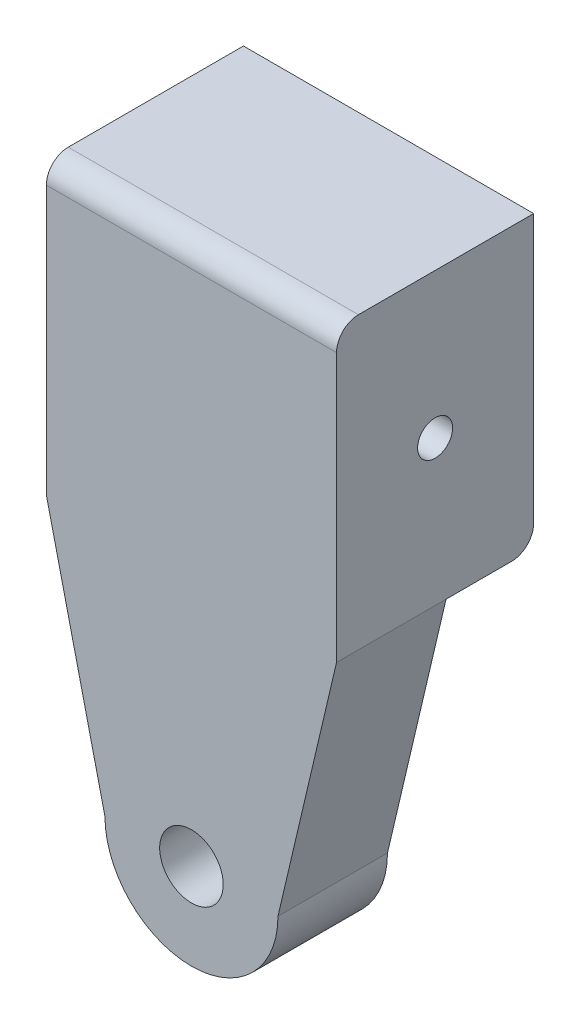
SolidWorks part; units mm, degrees
ref_plane "Alzado" through (0, 0, 0) normal (0, 0, 1) x (1, 0, 0)
ref_plane "Planta" through (0, 0, 0) normal (0, 1, 0) x (1, 0, 0)
ref_plane "Vista lateral" through (0, 0, 0) normal (1, 0, 0) x (0, 0, -1)
sketch "Croquis1" plane through (0, 0, 0) normal (0, 0, 1) x (1, 0, 0)
  line L0 (13.25, 13.25) -> (-13.25, 13.25)
  line L1 (10.25, -10.25) -> (-10.25, -10.25)
  line L2 (10.25, -10.25) -> (10.25, 10.25)
  line L3 (10.25, 10.25) -> (-10.25, 10.25)
  line L4 (-10.25, -10.25) -> (-10.25, 10.25)
  line L5 (10.25, -10.25) -> (-10.25, 10.25) construction
  line L6 (10.25, 10.25) -> (-10.25, -10.25) construction
  line L7 (-13.25, -13.25) -> (-13.25, 13.25)
  line L8 (13.25, -13.25) -> (-13.25, -13.25)
  line L9 (13.25, -13.25) -> (13.25, 13.25)
  point P0 (0, 0)
  dimension "D1" = 20.5
  dimension "D2" = 20.5
  dimension "D3" = 3
extrude "Saliente-Extruir1" add sketch "Croquis1" along normal mid plane 18
sketch "Croquis2" plane through (0, 0, 0) normal (0, 0, 1) x (1, 0, 0)
  line L0 (-7.9, -36) -> (-13.25, -13.25)
  line L1 (-13.25, -13.25) -> (13.25, -13.25) construction
  line L2 (-13.25, -13.25) -> (13.25, -13.25)
  line L3 (13.25, -13.25) -> (7.9, -36)
  line L4 (0, -35) -> (0, 55.3993) construction
  circle A0 centre (0, -36) radius 2.9
  arc A1 (-7.9, -36) -> (7.9, -36) centre (0, -36) ccw
  circle A2 centre (0, -36) radius 7.9 construction
  dimension "D1" = 5.8
  dimension "D3" = 36
  dimension "D4" = 26.5
  dimension "D2" = 5
extrude "Saliente-Extruir2" add sketch "Croquis2" along normal up to surface (9 mm away) and the other way blind 1 up to face at (0, 0, 9)
sketch "Croquis5" plane through (0, 0, 9) normal (0, 0, 1) x (1, 0, 0)
  line L0 (10.25, 10.25) -> (-10.25, 10.25) construction
  line L1 (10.25, 10.25) -> (-10.25, 10.25)
  line L2 (-10.25, 10.25) -> (-10.25, -10.25) construction
  line L3 (-10.25, 10.25) -> (-10.25, -10.25)
  line L4 (10.25, -10.25) -> (10.25, 10.25) construction
  line L5 (10.25, -10.25) -> (10.25, 10.25)
  line L6 (-10.25, -10.25) -> (10.25, -10.25) construction
  line L7 (-10.25, -10.25) -> (10.25, -10.25)
extrude "Saliente-Extruir3" add sketch "Croquis5" against normal blind 1
sketch "Croquis3" plane through (0, 0, 0) normal (1, 0, 0) x (0, 0, -1)
  line L0 (1, -28.25) -> (7.5, -13.25)
  line L1 (1, -36) -> (1, -13.25) construction
  line L3 (1, -13.25) -> (9, -13.25) construction
  dimension "D1" = 6.5
  dimension "D2" = 15
rib "Nervio6" sketch "Croquis3" sketch "Croquis3" thickness 10 extrusion direction parallel to sketch draft on no parameters "D1"=10
sketch "Croquis4" plane through (0, 0, 0) normal (1, 0, 0) x (0, 0, -1)
  circle A0 centre (0, 0) radius 1.6
  dimension "D1" = 3.2
extrude "Cortar-Extruir2" cut sketch "Croquis4" against normal mid plane 50 contours A0
fillet "Redondeo4" radius 2 1 edges at (0, 13.25, 9)
fillet "Redondeo5" radius 2 1 edges at (0, -13.25, -9)
